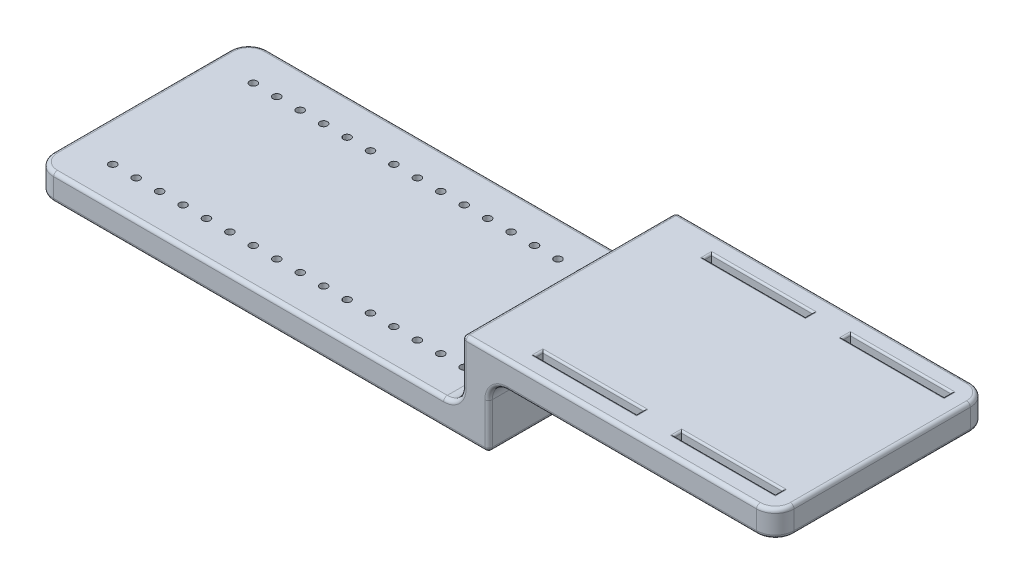
SolidWorks part; units mm, degrees
ref_plane "Front" through (0, 0, 0) normal (0, 0, 1) x (1, 0, 0)
ref_plane "Top" through (0, 0, 0) normal (0, 1, 0) x (1, 0, 0)
ref_plane "Right" through (0, 0, 0) normal (1, 0, 0) x (0, 0, -1)
sketch "Sketch2" plane through (0, 0, 0) normal (0, 0, 1) x (1, 0, 0)
  line L0 (0, 0) -> (80, 0)
  line L1 (0, 0) -> (0, -17)
  line L2 (0, -17) -> (-117.5, -17)
  dimension "D1" = 80
  dimension "D2" = 17
  dimension "D3" = 117.5
extrude "Extrude-Thin1" add sketch "Sketch2" along normal mid plane 57 thin thin type mid plane wall 7
fillet "Fillet6" radius 5 2 edges at (3.5, -3.5, 0) (-3.5, -13.5, 0)
sketch "Sketch5" plane through (0, 3.5, 0) normal (0, 1, 0) x (1, 0, 0)
  line L0 (80, -28.5) -> (80, 28.5) construction
  line L1 (11, -21.5) -> (38, -21.5)
  line L2 (11, -21.5) -> (11, -23.5)
  line L3 (11, -23.5) -> (38, -23.5)
  line L4 (38, -21.5) -> (38, -23.5)
  line L5 (48, -21.5) -> (75, -21.5)
  line L6 (48, -21.5) -> (48, -23.5)
  line L7 (48, -23.5) -> (75, -23.5)
  line L8 (75, -21.5) -> (75, -23.5)
  line L9 (80, -28.5) -> (-3.5, -28.5) construction
  line L10 (80, 28.5) -> (-3.5, 28.5) construction
  line L11 (11, 23.5) -> (38, 23.5)
  line L12 (11, 23.5) -> (11, 21.5)
  line L13 (11, 21.5) -> (38, 21.5)
  line L14 (38, 23.5) -> (38, 21.5)
  line L15 (48, 23.5) -> (75, 23.5)
  line L16 (48, 23.5) -> (48, 21.5)
  line L17 (48, 21.5) -> (75, 21.5)
  line L18 (75, 23.5) -> (75, 21.5)
  dimension "D1" = 27
  dimension "D2" = 10
  dimension "D3" = 2
  dimension "D4" = 5
  dimension "D5" = 5
  dimension "D6" = 5
extrude "Cut-Extrude1" cut sketch "Sketch5" against normal through all
sketch "Sketch6" plane through (0, -13.5, 0) normal (0, 1, 0) x (1, 0, 0)
  line L1 (-117.5, 0) -> (0, 0) construction
  line L2 (-117.5, -28.5) -> (-117.5, 28.5) construction
  line L4 (-3.5, -28.5) -> (-3.5, 28.5) construction
  circle A0 centre (-6.5, -18.75) radius 1
  circle A1 centre (-6.5, 18.75) radius 1
  dimension "D1" = 2
  dimension "D2" = 18.75
  dimension "D4" = 37.5
  dimension "D3" = 3
extrude "Cut-Extrude2" cut sketch "Sketch6" against normal through all and the other way blind 2
sketch "Sketch7" plane through (0, -20.5, 0) normal (0, -1, 0) x (1, 0, 0)
  circle A0 centre (-6.5, 18.75) radius 2
  circle A1 centre (-6.5, -18.75) radius 2
  dimension "D1" = 4
extrude "Cut-Extrude3" cut sketch "Sketch7" against normal offset from surface (1.75 mm away) 5.25 up to face at (-63, -13.5, 0)
fillet "Fillet2" radius 0.5 2 edges at (-4.5, -20.5, -18.75) (-4.5, -20.5, 18.75)
pattern_linear "LPattern1" count 9 spacing 12.5 along (-1, 0, 0) of "Cut-Extrude3", "Fillet2", "Cut-Extrude2"
fillet "Fillet3" radius 5 4 edges at (80, 0, -28.5) (80, 0, 28.5) (-117.5, -17, -28.5) (-117.5, -17, 28.5)
fillet "Fillet4" radius 1 30 edges at (-117.5, -13.5, 0) (-117.5, -20.5, 0) (-54.5, -20.5, -28.5) (3.5, -14.5, -28.5) (41.75, -3.5, -28.5) (35.75, 3.5, -28.5) (-3.5, -2.5, -28.5) (-60.5, -13.5, -28.5) (80, -3.5, 0) (80, 3.5, 0) (35.75, 3.5, 28.5) (41.75, -3.5, 28.5) (3.5, -14.5, 28.5) (-54.5, -20.5, 28.5) (-60.5, -13.5, 28.5) (-3.5, -2.5, 28.5) (-3.5, 3.5, 0) (3.5, -20.5, 0) (-116.0355, -20.5, -27.0355) (-116.0355, -20.5, 27.0355) (-116.0355, -13.5, -27.0355) (-116.0355, -13.5, 27.0355) (78.5355, 3.5, -27.0355) (78.5355, 3.5, 27.0355) (78.5355, -3.5, -27.0355) (78.5355, -3.5, 27.0355) (-4.9645, -12.0355, -28.5) (4.9645, -4.9645, -28.5) (4.9645, -4.9645, 28.5) (-4.9645, -12.0355, 28.5)
fillet "Fillet5" radius 0.5 32 edges at (61.5, -3.5, 21.5) (75, -3.5, 22.5) (61.5, -3.5, 23.5) (48, -3.5, 22.5) (24.5, -3.5, 21.5) (38, -3.5, 22.5) (24.5, -3.5, 23.5) (11, -3.5, 22.5) (24.5, -3.5, -23.5) (38, -3.5, -22.5) (24.5, -3.5, -21.5) (11, -3.5, -22.5) (61.5, -3.5, -23.5) (75, -3.5, -22.5) (61.5, -3.5, -21.5) (48, -3.5, -22.5) (38, 3.5, -22.5) (24.5, 3.5, -23.5) (11, 3.5, -22.5) (24.5, 3.5, -21.5) (75, 3.5, -22.5) (61.5, 3.5, -23.5) (48, 3.5, -22.5) (61.5, 3.5, -21.5) (75, 3.5, 22.5) (61.5, 3.5, 21.5) (48, 3.5, 22.5) (61.5, 3.5, 23.5) (38, 3.5, 22.5) (24.5, 3.5, 21.5) (11, 3.5, 22.5) (24.5, 3.5, 23.5)
sketch "Sketch8" plane through (0, -20.5, 0) normal (0, -1, 0) x (1, 0, 0)
  line L0 (2.5, 0) -> (-116.5, 0) construction
  line L2 (-116.5, 23.5) -> (-116.5, -23.5) construction
  line L3 (2.5, -2.5) -> (-116.5, -2.5) construction
  line L5 (2.5, -27.5) -> (2.5, 27.5) construction
  text T0 "KM-MB50-9-17-A" font "Calibri" height 5
  point P2 (0, 0)
  point P5 (0, 0)
  point P8 (0, 0)
  point P12 (0, 0)
  point P14 (0, 0)
  dimension "D1" = 2.5
extrude "Part Number Extrude Cut" cut sketch "Sketch8" against normal blind 0.6
sketch "Sketch10" plane through (0, -20.5, 0) normal (0, -1, 0) x (1, 0, 0)
  line L0 (-6.5, -18.75) -> (-12.75, -18.75) construction
  line L1 (-12.75, 18.75) -> (-12.75, -18.75) construction
  line L2 (-6.5, 18.75) -> (-12.75, 18.75) construction
  circle A0 centre (-12.75, -18.75) radius 1
  circle A1 centre (-12.75, 18.75) radius 1
  dimension "D2" = 2
  dimension "D1" = 6.25
extrude "Cut-Extrude4" cut sketch "Sketch10" against normal up to surface (7 mm away) up to face at (-43, -13.5, -18.75)
fillet "Fillet7" radius 0.5 2 edges at (-11.75, -20.5, -18.75) (-11.75, -20.5, 18.75)
pattern_linear "LPattern2" count 8 spacing 12.5 along (-1, 0, 0) of "Cut-Extrude4", "Fillet7"
equation "\"D2@Sketch6\"=37.5/2"
equation "\"Screw Hole Spacing\"= 12.5mm"
equation "\"Screw Hole Qty\"= 9"
equation "\"D1@LPattern1\"=\"Screw Hole Qty\""
equation "\"D3@Sketch2\"=\"Screw Hole Qty\"*\"Screw Hole Spacing\"+5"
equation "\"Drop Distance\"= 17mm"
equation "\"D2@Sketch2\"=\"Drop Distance\""
equation "\"D1@Sketch10\"=\"Screw Hole Spacing\"/2"
equation "\"D3@LPattern2\"=\"Screw Hole Spacing\""
equation "\"D1@LPattern2\"=\"Screw Hole Qty\"-1"
